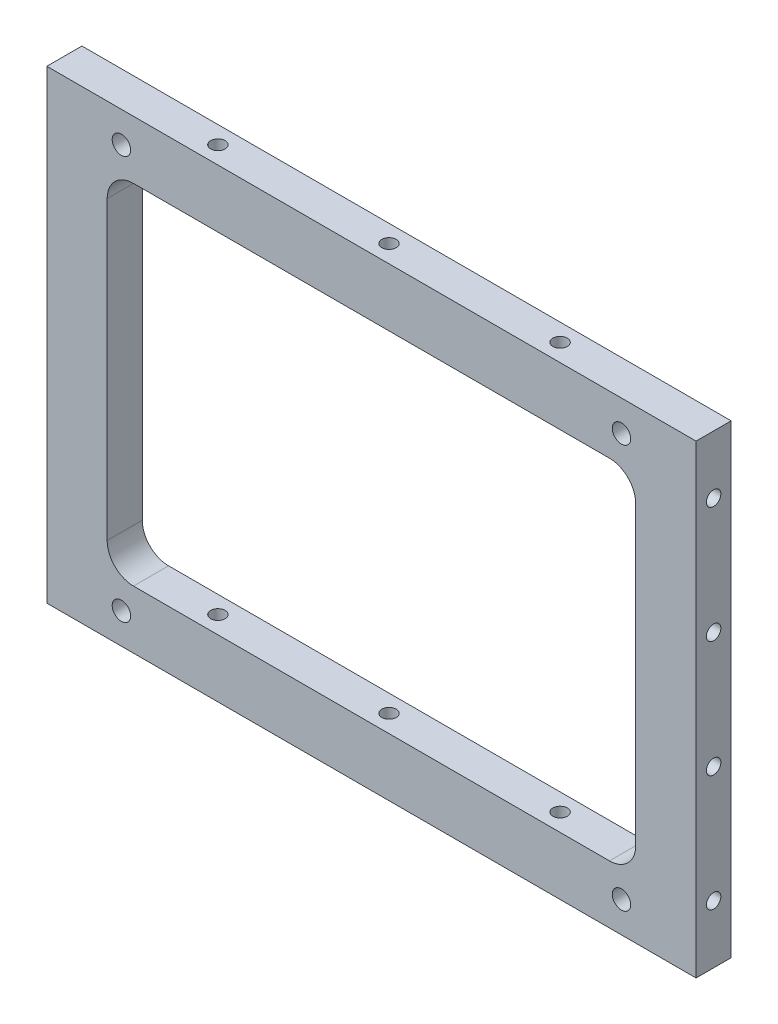
SolidWorks part; units mm, degrees
ref_plane "Front Plane" through (0, 0, 0) normal (0, 0, 1) x (1, 0, 0)
ref_plane "Top Plane" through (0, 0, 0) normal (0, 1, 0) x (1, 0, 0)
ref_plane "Right Plane" through (0, 0, 0) normal (1, 0, 0) x (0, 0, -1)
sketch "Sketch1" plane through (0, 0, 0) normal (0, 0, 1) x (1, 0, 0)
  line L1 (-74, 53) -> (74, 53)
  line L2 (-74, 53) -> (-74, -53)
  line L3 (-74, -53) -> (74, -53)
  line L4 (74, 53) -> (74, -53)
  line L5 (-74, 53) -> (74, -53) construction
  line L6 (-74, -53) -> (74, 53) construction
  point P0 (0, 0)
  dimension "D1" = 148
  dimension "D2" = 106
extrude "Boss-Extrude1" add sketch "Sketch1" against normal blind 8
sketch "Sketch2" plane through (0, 0, 0) normal (0, 0, 1) x (1, 0, 0)
  line L0 (0, 53) -> (0, -53) construction
  line L1 (74, 53) -> (-74, 53) construction
  line L2 (-74, -53) -> (74, -53) construction
  line L3 (-57, 46) -> (57, 46)
  line L4 (-57, 46) -> (-57, -46)
  line L5 (-57, -46) -> (57, -46)
  line L6 (57, 46) -> (57, -46)
  line L7 (-57, 46) -> (57, -46) construction
  line L8 (-57, -46) -> (57, 46) construction
  line L9 (-54.25, 39.75) -> (54.25, 39.75)
  line L10 (-60.25, 33.75) -> (-60.25, -33.75)
  line L11 (-54.25, -39.75) -> (54.25, -39.75)
  line L12 (60.25, 33.75) -> (60.25, -33.75)
  line L13 (-60.25, 39.75) -> (60.25, -39.75) construction
  line L14 (-60.25, -39.75) -> (60.25, 39.75) construction
  circle A0 centre (-57, 46) radius 2.1
  circle A1 centre (57, 46) radius 2.1
  circle A2 centre (-57, -46) radius 2.1
  circle A3 centre (57, -46) radius 2.1
  arc A4 (54.25, -39.75) -> (60.25, -33.75) centre (54.25, -33.75) ccw
  arc A5 (-60.25, -33.75) -> (-54.25, -39.75) centre (-54.25, -33.75) ccw
  arc A6 (54.25, 39.75) -> (60.25, 33.75) centre (54.25, 33.75) cw
  arc A7 (-54.25, 39.75) -> (-60.25, 33.75) centre (-54.25, 33.75) ccw
  point P6 (0, 0)
  point P15 (0, 0)
  point P33 (0, 0)
  dimension "D3" = 4.2
  dimension "D4" = 6
  dimension "D1" = 114
  dimension "D2" = 92
extrude "Cut-Extrude1" cut sketch "Sketch2" against normal up to next contours A6 L6 A4 L12 | L9 A7 L4 A5 L11 A4 L6 A6 | L4 A7 L10 A5 | L6 A1 L3 | L3 A1 L6 | L3 A0 L4 | L4 A0 L3 | L5 A2 L4 | L4 A2 L5 | L6 A3 L5 | L5 A3 L6 region at (-57.2971, 46.2971, 0) region at (-56.1087, 45.1087, 0) region at (57.2971, 46.2971, 0) region at (56.1087, 45.1087, 0) region at (0, 0, 0) region at (-58.5957, 0, 0) region at (58.5957, 0, 0) region at (-56.1087, -45.1087, 0) region at (-57.2971, -46.2971, 0) region at (57.2971, -46.2971, 0) region at (56.1087, -45.1087, 0)
sketch "Sketch3" plane through (0, -53, 0) normal (0, -1, 0) x (1, 0, 0)
  line L0 (-74, -4) -> (74, -4) construction
  line L1 (-74, -8) -> (-74, 0) construction
  line L2 (74, -8) -> (74, 0) construction
  circle A0 centre (-39, -4) radius 1.65
  circle A1 centre (0, -4) radius 1.65
  circle A2 centre (39, -4) radius 1.65
  dimension "D1" = 3.3
  dimension "D2" = 35
  dimension "D3" = 3
extrude "Cut-Extrude2" cut sketch "Sketch3" against normal through all
sketch "Sketch5" plane through (74, 0, 0) normal (1, 0, 0) x (0, 0, -1)
  line L0 (0, 0) -> (8, 0) construction
  line L2 (8, -53) -> (8, 53) construction
  line L3 (4, 53) -> (4, -53) construction
  line L8 (8, 53) -> (0, 53) construction
  line L11 (8, -53) -> (0, -53) construction
  circle A4 centre (4, 39.75) radius 1.65
  circle A5 centre (4, 13.25) radius 1.65
  circle A6 centre (4, -13.25) radius 1.65
  circle A7 centre (4, -39.75) radius 1.65
  dimension "D1" = 3.3
  dimension "D2" = 13.25
extrude "Cut-Extrude3" cut sketch "Sketch5" against normal blind 10 contours A4 | A5 | A6 | A7 region at (74, 39.75, -4) region at (74, 13.25, -4) region at (74, -13.25, -4) region at (74, -39.75, -4)
sketch "Sketch6" plane through (-74, 0, 0) normal (-1, 0, 0) x (0, 0, 1)
  line L0 (-8, 53) -> (0, 53) construction
  line L2 (-8, 0) -> (0, 0) construction
  line L3 (-4, 53) -> (-4, -53) construction
  circle A0 centre (-4, 39.75) radius 1.65
  circle A1 centre (-4, 13.25) radius 1.65
  circle A2 centre (-4, -13.25) radius 1.65
  circle A3 centre (-4, -39.75) radius 1.65
  dimension "D1" = 3.3
  dimension "D2" = 13.25
  dimension "D3" = 26.5
extrude "Cut-Extrude4" cut sketch "Sketch6" against normal blind 10
